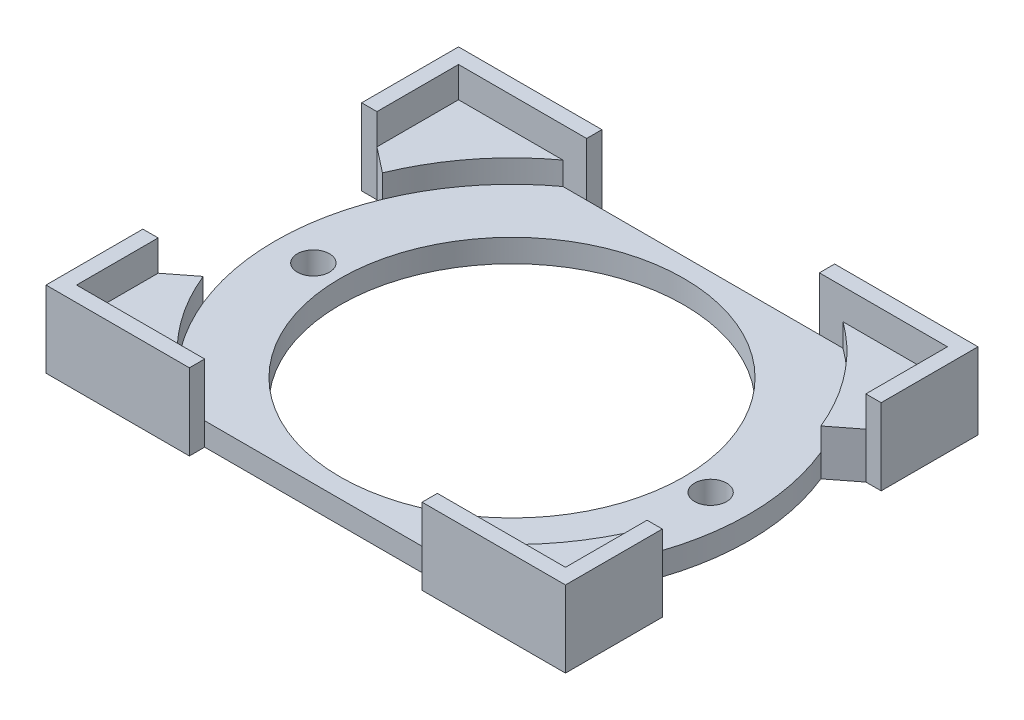
SolidWorks part; units mm, degrees
ref_plane "Front Plane" through (0, 0, 0) normal (0, 0, 1) x (1, 0, 0)
ref_plane "Top Plane" through (0, 0, 0) normal (0, 1, 0) x (1, 0, 0)
ref_plane "Right Plane" through (0, 0, 0) normal (1, 0, 0) x (0, 0, -1)
sketch "Sketch1" plane through (0, 0, 0) normal (0, 1, 0) x (1, 0, 0)
  line L0 (-32, 25) -> (32, -25) construction
  line L1 (32, -25) -> (-32, -25)
  line L2 (32, -25) -> (32, 25)
  line L3 (32, 25) -> (-32, 25)
  line L4 (-32, -25) -> (-32, 25)
  line L5 (0, 25) -> (0, -25) construction
  line L6 (32, 0) -> (-32, 0) construction
  line L7 (-32, -25) -> (32, 25) construction
  line L8 (-18.3303, 25) -> (-11.2626, 19.4783)
  line L9 (-28.6924, 11.7365) -> (-21.6247, 6.2148)
  line L10 (-32, -25) -> (-17.7305, -13.852)
  line L11 (18.3303, 25) -> (11.2626, 19.4783)
  line L12 (-11.2626, -19.4783) -> (-18.3303, -25)
  line L13 (-28.6924, 11.7365) -> (-32, 14.3205)
  line L14 (-21.6247, -6.2148) -> (-32, -14.3205)
  line L15 (28.6924, 11.7365) -> (21.6247, 6.2148)
  line L16 (21.6247, -6.2148) -> (32, -14.3205)
  line L17 (11.2626, -19.4783) -> (18.3303, -25)
  line L18 (28.6924, 11.7365) -> (32, 14.3205)
  line L19 (15.2315, 27) -> (15.2315, 25)
  line L20 (34, -27) -> (-34, -27)
  line L21 (34, -27) -> (34, 27)
  line L22 (34, 27) -> (-34, 27)
  line L23 (-34, -27) -> (-34, 27)
  line L24 (0, 27) -> (0, -27) construction
  line L25 (34, 0) -> (-34, 0) construction
  line L26 (15.2315, 25) -> (32, 25)
  line L27 (32, 14.3205) -> (34, 14.3205)
  line L28 (34, 14.3205) -> (34, 27)
  line L29 (-32, 14.3205) -> (-34, 14.3205)
  line L30 (-15.2315, 27) -> (-15.2315, 25)
  line L31 (32, -14.3205) -> (34, -14.3205)
  line L32 (15.2315, -27) -> (15.2315, -25)
  line L33 (-15.2315, -27) -> (-15.2315, -25)
  line L34 (-32, -14.3205) -> (-34, -14.3205)
  circle A0 centre (0, 0) radius 22.5
  arc A1 (-18.3303, 25) -> (-18.3303, -25) centre (0, 0) ccw
  circle A2 centre (-26, 0) radius 2.1
  circle A3 centre (26, 0) radius 2.1
  arc A4 (18.3303, -25) -> (18.3303, 25) centre (0, 0) ccw
  point P33 (15.2315, 27)
  dimension "D1" = 45
  dimension "D2" = 62
  dimension "D5" = 4.2
  dimension "D3" = 64
  dimension "D4" = 50
  dimension "D6" = 26
  dimension "D7" = 68
  dimension "D8" = 54
extrude "Boss-Extrude1" add sketch "Sketch1" along normal blind 10 contours L4 L34 L23 L20 L33 L1 | L32 L20 L21 L31 L2 L1 | L2 L27 L21 L22 L19 L3 | L30 L22 L23 L29 L4 L3 region at (32.2265, 0, 19.6603) region at (32.2265, 0, -19.6603) region at (-15.458, 0, 26) region at (-16.7809, 0, -25.2265)
extrude "Boss-Extrude2" add sketch "Sketch1<9>" along normal blind 3 contours A1 L3 L4 L13 | L8 A1 L9 A0 | A0 L11 L3 L8 | L15 A4 L11 A0 | A4 L18 L2 L3 | L16 A4 L15 A0 A3 | L14 A1 L10 A0 | L9 A1 L14 A0 A2 | A1 L14 L4 L10 | A1 L10 L1 | L10 A1 L12 A0 | A0 L12 L1 L17 | L17 A4 L16 A0 | A4 L1 L2 L16 region at (27.5253, 0, 20.1834) region at (0, 0, 23.1509) region at (20.7114, 0, 16.1808) region at (25.3141, 0, 8.7765) region at (27.5253, 0, -20.1834) region at (-18.0979, 0, 19.5261) region at (20.7114, 0, -16.1808) region at (-25.0676, 0, 23.0669) region at (-23.325, 0, 12.8355) region at (0, 0, -23.1509) region at (-29.2139, 0, 18.2023) region at (-25.3141, 0, 8.7765) region at (-20.7114, 0, -16.1808) region at (-27.5253, 0, -20.1834)
sketch "Sketch1<9>" plane through (0, 0, 0) normal (0, 1, 0) x (1, 0, 0) same geometry as "Sketch1"
extrude "Boss-Extrude3" add sketch "Sketch1<11>" along normal blind 6 contours A1 L3 L4 L13 | A4 L18 L2 L3 | A4 L1 L2 L16 | A1 L14 L4 L10 | A1 L10 L1 region at (27.5253, 0, 20.1834) region at (27.5253, 0, -20.1834) region at (-25.0676, 0, 23.0669) region at (-29.2139, 0, 18.2023) region at (-27.5253, 0, -20.1834)
sketch "Sketch1<11>" plane through (0, 0, 0) normal (0, 1, 0) x (1, 0, 0) same geometry as "Sketch1"
